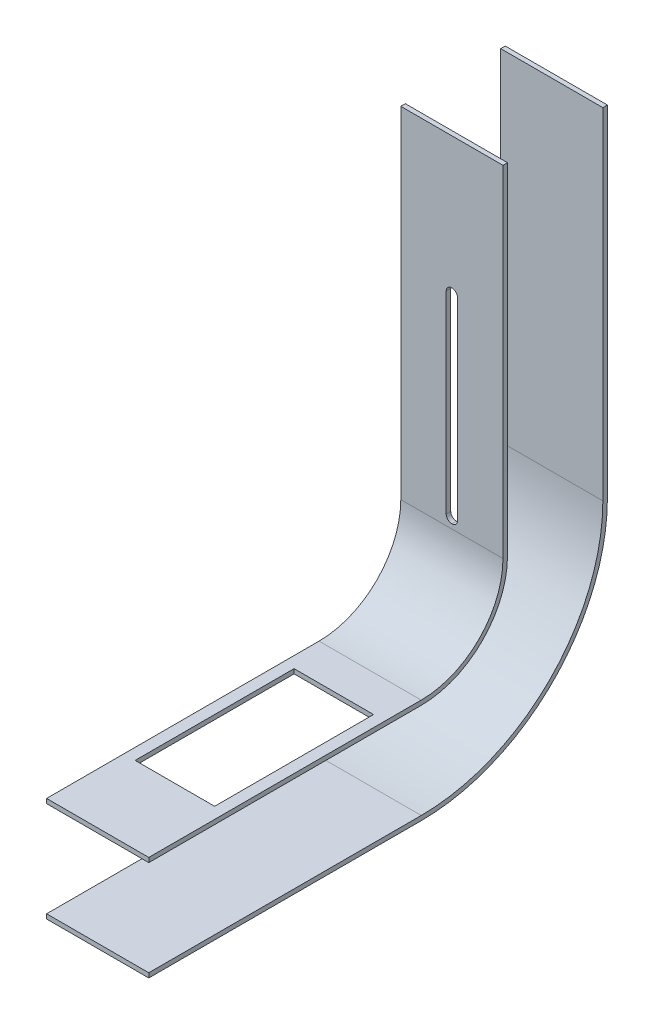
SolidWorks part; units mm, degrees
ref_plane "Front Plane" through (0, 0, 0) normal (0, 0, 1) x (1, 0, 0)
ref_plane "Top Plane" through (0, 0, 0) normal (0, 1, 0) x (1, 0, 0)
ref_plane "Right Plane" through (0, 0, 0) normal (1, 0, 0) x (0, 0, -1)
sketch "Sketch1" plane through (0, 0, 0) normal (1, 0, 0) x (0, 0, -1)
  line L0 (0, 0) -> (97.8551, 0) construction
  line L1 (0, 0) -> (0, -76) construction
  line L2 (0, -38) -> (-120, -38)
  line L3 (0, -36) -> (-120, -36)
  line L4 (-120, -80) -> (0, -80)
  line L5 (0, -80) -> (-0.0876, -80.2988)
  line L6 (80, 0) -> (80, 150)
  line L7 (36, 150) -> (36, 0)
  line L8 (38, 150) -> (38, 0)
  line L9 (82, 0) -> (82, 150)
  line L10 (-120, -82) -> (0, -82)
  line L11 (-120, -36) -> (-120, -38)
  line L12 (-120, -80) -> (-120, -82)
  line L13 (36, 150) -> (38, 150)
  line L14 (80, 150) -> (82, 150)
  arc A0 (0, -80) -> (80, 0) centre (0, 0) ccw
  arc A1 (0, -38) -> (38, 0) centre (0, 0) ccw
  arc A2 (0, -36) -> (36, 0) centre (0, 0) ccw
  arc A3 (0, -82) -> (82, 0) centre (0, 0) ccw
  dimension "D1" = 80
  dimension "D2" = 42
  dimension "D3" = 150
  dimension "D4" = 120
  dimension "D5" = 2
  dimension "D6" = 2
extrude "Boss-Extrude1" add sketch "Sketch1" along normal blind 45 contours A2 L3 L11 L2 A1 L8 L13 L7 | L10 A3 L9 L14 L6 A0 L4 L12 region at (0, -37.7544, 60) region at (0, -80.3076, 60)
sketch "Sketch2" plane through (0, 0, -36) normal (0, 0, 1) x (1, 0, 0)
  line L0 (22.5, 0) -> (22.5, 74.0659) construction
  line L1 (45, 0) -> (0, 0) construction
  line L3 (20, 92) -> (25, 92)
  line L4 (20, 92) -> (20, 2)
  line L5 (20, 2) -> (25, 2)
  line L6 (25, 92) -> (25, 2)
  line L7 (20, 92) -> (25, 2) construction
  line L8 (20, 2) -> (25, 92) construction
  point P4 (22.5, 47)
  dimension "D1" = 5
  dimension "D2" = 90
  dimension "D3" = 92
extrude "Cut-Extrude1" cut sketch "Sketch2" against normal blind 5
sketch "Sketch3" plane through (0, -36, 0) normal (0, 1, 0) x (1, 0, 0)
  line L0 (22.5, -120) -> (22.5, 0) construction
  line L1 (45, -120) -> (0, -120) construction
  line L2 (45, 0) -> (0, 0) construction
  line L4 (5, -86) -> (40, -86)
  line L5 (5, -86) -> (5, -16)
  line L6 (5, -16) -> (40, -16)
  line L7 (40, -86) -> (40, -16)
  line L8 (5, -86) -> (40, -16) construction
  line L9 (5, -16) -> (40, -86) construction
  point P6 (22.5, -51)
  dimension "D1" = 35
  dimension "D2" = 70
  dimension "D3" = 16
extrude "Cut-Extrude2" cut sketch "Sketch3" against normal blind 5
fillet "Fillet1" radius 2.5 4 edges at (25, 92, -37) (20, 92, -37) (25, 2, -37) (20, 2, -37)
